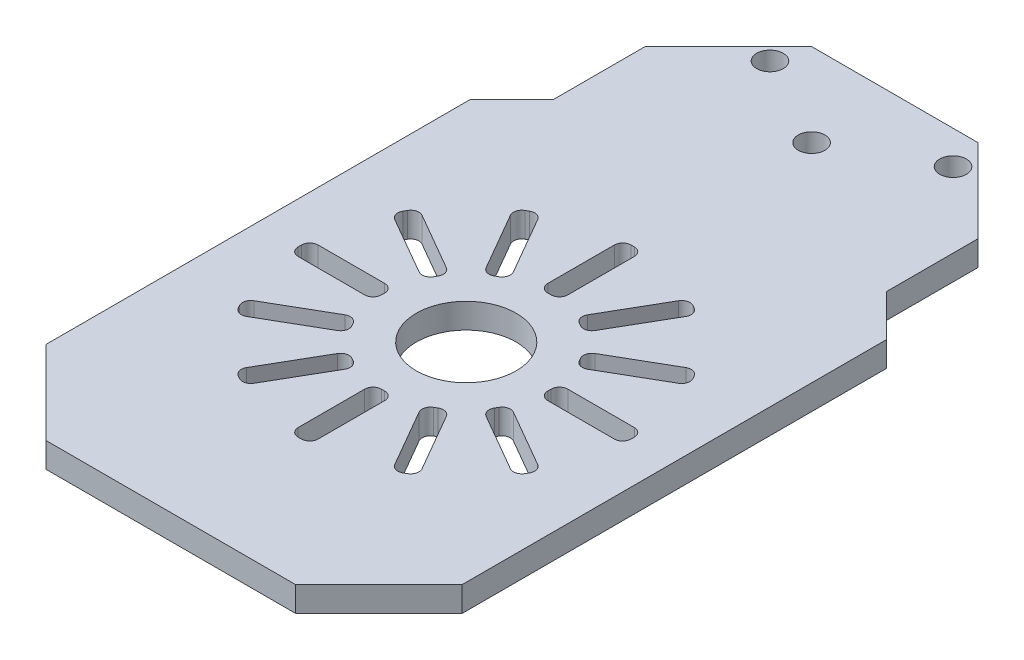
SolidWorks part; units mm, degrees
material "Thornel Mat VMA"
ref_plane "前视基准面" through (0, 0, 0) normal (0, 0, 1) x (1, 0, 0)
ref_plane "上视基准面" through (0, 0, 0) normal (0, 1, 0) x (1, 0, 0)
ref_plane "右视基准面" through (0, 0, 0) normal (1, 0, 0) x (0, 0, -1)
sketch "草图1" plane through (0, 0, 0) normal (0, 1, 0) x (1, 0, 0)
  line L0 (0, -1000) -> (0, 49000) construction
  line L1 (-20, 8) -> (20, 8)
  line L2 (-20, 8) -> (-20, -8)
  line L3 (-20, -8) -> (20, -8)
  line L4 (20, 8) -> (20, -8)
  line L5 (-20, 8) -> (20, -8) construction
  line L6 (-20, -8) -> (20, 8) construction
  line L7 (-25, -79) -> (25, -79)
  line L8 (-25, -79) -> (-25, -8)
  line L9 (-25, -8) -> (25, -8)
  line L10 (25, -79) -> (25, -8)
  line L11 (-25, -79) -> (25, -8) construction
  line L12 (-25, -8) -> (25, -79) construction
  circle A0 centre (-11, 4) radius 1.6
  circle A1 centre (0, -2) radius 1.6
  circle A2 centre (11, 4) radius 1.6
  point P0 (0, 0)
  point P6 (0, -43.5)
  dimension "D3" = 3.2
  dimension "D4" = 3.2
  dimension "D1" = 16
  dimension "D2" = 40
  dimension "D5" = 6
  dimension "D6" = 4
  dimension "D7" = 11
  dimension "D8" = 71
  dimension "D9" = 50
extrude "凸台-拉伸1" add sketch "草图1" along normal blind 3 contours L7 L10 L9 L3 L8 | L4 L1 L2 L3 A0 A1 A2 region at (0, 0, 0.0784) region at (0, 0, 43.5)
chamfer "倒角1" distance 10 angle 45 6 edges at (-25, 1.5, 8) (25, 1.5, 8) (-20, 1.5, -8) (20, 1.5, -8) (25, 1.5, 79) (-25, 1.5, 79)
sketch "草图2" [suppressed] plane through (0, 3, 0) normal (0, 1, 0) x (1, 0, 0)
  line L0 (0, -1000) -> (0, 49000) construction
  line L1 (18, -71.4131) -> (12, -26.4131) construction
  line L2 (-7.5, -15.8094) -> (7.5, -15.8094)
  line L3 (-7.5, -15.8094) -> (-7.5, -25.8094)
  line L4 (-7.5, -25.8094) -> (7.5, -25.8094)
  line L5 (7.5, -15.8094) -> (7.5, -25.8094)
  line L6 (-7.5, -15.8094) -> (7.5, -25.8094) construction
  line L7 (-7.5, -25.8094) -> (7.5, -15.8094) construction
  line L8 (-18, -26.4131) -> (-12, -26.4131)
  line L9 (-18, -26.4131) -> (-18, -71.4131)
  line L10 (-18, -71.4131) -> (-12, -71.4131)
  line L11 (-12, -26.4131) -> (-12, -71.4131)
  line L12 (-18, -26.4131) -> (-12, -71.4131) construction
  line L13 (-18, -71.4131) -> (-12, -26.4131) construction
  line L14 (18, -26.4131) -> (12, -71.4131) construction
  line L15 (12, -26.4131) -> (12, -71.4131)
  line L16 (18, -71.4131) -> (12, -71.4131)
  line L17 (18, -26.4131) -> (18, -71.4131)
  line L18 (18, -26.4131) -> (12, -26.4131)
  point P1 (0, -20.8094)
  point P8 (-15, -48.9131)
  point P17 (15, -48.9131)
  dimension "D1" = 15
  dimension "D2" = 10
  dimension "D3" = 15
  dimension "D4" = 6
  dimension "D5" = 45
sketch "草图3" plane through (0, 3, 0) normal (0, 1, 0) x (1, 0, 0)
  line L0 (-25, -18) -> (25, -69) construction
  line L1 (0, -43.5) -> (0, -58.5) construction
  line L2 (-6.5392, -52.4263) -> (-10.5392, -59.3545)
  line L3 (-0.2, -53.5) -> (0.2, -53.5)
  line L4 (-1.2, -54.5) -> (-1.2, -62.5)
  line L5 (-0.2, -63.5) -> (0.2, -63.5)
  line L6 (1.2, -54.5) -> (1.2, -62.5)
  line L7 (-1.2, -53.5) -> (1.2, -63.5) construction
  line L8 (-1.2, -63.5) -> (1.2, -53.5) construction
  line L9 (-4.4608, -53.6263) -> (-8.4608, -60.5545)
  line L10 (-5.1732, -52.0603) -> (-4.8268, -52.2603)
  line L11 (-10.1732, -60.7205) -> (-9.8268, -60.9205)
  line L12 (-10.1263, -47.9608) -> (-17.0545, -51.9608)
  line L13 (-8.9263, -50.0392) -> (-15.8545, -54.0392)
  line L14 (-8.7603, -48.3268) -> (-8.5603, -48.6732)
  line L15 (-17.4205, -53.3268) -> (-17.2205, -53.6732)
  line L16 (-11, -42.3) -> (-19, -42.3)
  line L17 (-11, -44.7) -> (-19, -44.7)
  line L18 (-10, -43.3) -> (-10, -43.7)
  line L19 (-20, -43.3) -> (-20, -43.7)
  line L20 (-8.9263, -36.9608) -> (-15.8545, -32.9608)
  line L21 (-10.1263, -39.0392) -> (-17.0545, -35.0392)
  line L22 (-8.5603, -38.3268) -> (-8.7603, -38.6732)
  line L23 (-17.2205, -33.3268) -> (-17.4205, -33.6732)
  line L24 (-4.4608, -33.3737) -> (-8.4608, -26.4455)
  line L25 (-6.5392, -34.5737) -> (-10.5392, -27.6455)
  line L26 (-4.8268, -34.7397) -> (-5.1732, -34.9397)
  line L27 (-9.8268, -26.0795) -> (-10.1732, -26.2795)
  line L28 (1.2, -32.5) -> (1.2, -24.5)
  line L29 (-1.2, -32.5) -> (-1.2, -24.5)
  line L30 (0.2, -33.5) -> (-0.2, -33.5)
  line L31 (0.2, -23.5) -> (-0.2, -23.5)
  line L32 (6.5392, -34.5737) -> (10.5392, -27.6455)
  line L33 (4.4608, -33.3737) -> (8.4608, -26.4455)
  line L34 (5.1732, -34.9397) -> (4.8268, -34.7397)
  line L35 (10.1732, -26.2795) -> (9.8268, -26.0795)
  line L36 (10.1263, -39.0392) -> (17.0545, -35.0392)
  line L37 (8.9263, -36.9608) -> (15.8545, -32.9608)
  line L38 (8.7603, -38.6732) -> (8.5603, -38.3268)
  line L39 (17.4205, -33.6732) -> (17.2205, -33.3268)
  line L40 (11, -44.7) -> (19, -44.7)
  line L41 (11, -42.3) -> (19, -42.3)
  line L42 (10, -43.7) -> (10, -43.3)
  line L43 (20, -43.7) -> (20, -43.3)
  line L44 (8.9263, -50.0392) -> (15.8545, -54.0392)
  line L45 (10.1263, -47.9608) -> (17.0545, -51.9608)
  line L46 (8.5603, -48.6732) -> (8.7603, -48.3268)
  line L47 (17.2205, -53.6732) -> (17.4205, -53.3268)
  line L48 (4.4608, -53.6263) -> (8.4608, -60.5545)
  line L49 (6.5392, -52.4263) -> (10.5392, -59.3545)
  line L50 (4.8268, -52.2603) -> (5.1732, -52.0603)
  line L51 (9.8268, -60.9205) -> (10.1732, -60.7205)
  line L52 (0, -43.5) -> (-0.2, -53.5) construction
  circle A0 centre (0, -43.5) radius 6
  arc A1 (0.2, -63.5) -> (1.2, -62.5) centre (0.2, -62.5) ccw
  arc A2 (-1.2, -62.5) -> (-0.2, -63.5) centre (-0.2, -62.5) ccw
  arc A3 (0.2, -53.5) -> (1.2, -54.5) centre (0.2, -54.5) cw
  arc A4 (-0.2, -53.5) -> (-1.2, -54.5) centre (-0.2, -54.5) ccw
  arc A5 (-5.1732, -52.0603) -> (-6.5392, -52.4263) centre (-5.6732, -52.9263) ccw
  arc A6 (-4.8268, -52.2603) -> (-4.4608, -53.6263) centre (-5.3268, -53.1263) cw
  arc A7 (-9.8268, -60.9205) -> (-8.4608, -60.5545) centre (-9.3268, -60.0545) ccw
  arc A8 (-10.5392, -59.3545) -> (-10.1732, -60.7205) centre (-9.6732, -59.8545) ccw
  arc A9 (-8.7603, -48.3268) -> (-10.1263, -47.9608) centre (-9.6263, -48.8268) ccw
  arc A10 (-8.5603, -48.6732) -> (-8.9263, -50.0392) centre (-9.4263, -49.1732) cw
  arc A11 (-17.2205, -53.6732) -> (-15.8545, -54.0392) centre (-16.3545, -53.1732) ccw
  arc A12 (-17.0545, -51.9608) -> (-17.4205, -53.3268) centre (-16.5545, -52.8268) ccw
  arc A13 (-10, -43.3) -> (-11, -42.3) centre (-11, -43.3) ccw
  arc A14 (-10, -43.7) -> (-11, -44.7) centre (-11, -43.7) cw
  arc A15 (-20, -43.7) -> (-19, -44.7) centre (-19, -43.7) ccw
  arc A16 (-19, -42.3) -> (-20, -43.3) centre (-19, -43.3) ccw
  arc A17 (-8.5603, -38.3268) -> (-8.9263, -36.9608) centre (-9.4263, -37.8268) ccw
  arc A18 (-8.7603, -38.6732) -> (-10.1263, -39.0392) centre (-9.6263, -38.1732) cw
  arc A19 (-17.4205, -33.6732) -> (-17.0545, -35.0392) centre (-16.5545, -34.1732) ccw
  arc A20 (-15.8545, -32.9608) -> (-17.2205, -33.3268) centre (-16.3545, -33.8268) ccw
  arc A21 (-4.8268, -34.7397) -> (-4.4608, -33.3737) centre (-5.3268, -33.8737) ccw
  arc A22 (-5.1732, -34.9397) -> (-6.5392, -34.5737) centre (-5.6732, -34.0737) cw
  arc A23 (-10.1732, -26.2795) -> (-10.5392, -27.6455) centre (-9.6732, -27.1455) ccw
  arc A24 (-8.4608, -26.4455) -> (-9.8268, -26.0795) centre (-9.3268, -26.9455) ccw
  arc A25 (0.2, -33.5) -> (1.2, -32.5) centre (0.2, -32.5) ccw
  arc A26 (-0.2, -33.5) -> (-1.2, -32.5) centre (-0.2, -32.5) cw
  arc A27 (-0.2, -23.5) -> (-1.2, -24.5) centre (-0.2, -24.5) ccw
  arc A28 (1.2, -24.5) -> (0.2, -23.5) centre (0.2, -24.5) ccw
  arc A29 (5.1732, -34.9397) -> (6.5392, -34.5737) centre (5.6732, -34.0737) ccw
  arc A30 (4.8268, -34.7397) -> (4.4608, -33.3737) centre (5.3268, -33.8737) cw
  arc A31 (9.8268, -26.0795) -> (8.4608, -26.4455) centre (9.3268, -26.9455) ccw
  arc A32 (10.5392, -27.6455) -> (10.1732, -26.2795) centre (9.6732, -27.1455) ccw
  arc A33 (8.7603, -38.6732) -> (10.1263, -39.0392) centre (9.6263, -38.1732) ccw
  arc A34 (8.5603, -38.3268) -> (8.9263, -36.9608) centre (9.4263, -37.8268) cw
  arc A35 (17.2205, -33.3268) -> (15.8545, -32.9608) centre (16.3545, -33.8268) ccw
  arc A36 (17.0545, -35.0392) -> (17.4205, -33.6732) centre (16.5545, -34.1732) ccw
  arc A37 (10, -43.7) -> (11, -44.7) centre (11, -43.7) ccw
  arc A38 (10, -43.3) -> (11, -42.3) centre (11, -43.3) cw
  arc A39 (20, -43.3) -> (19, -42.3) centre (19, -43.3) ccw
  arc A40 (19, -44.7) -> (20, -43.7) centre (19, -43.7) ccw
  arc A41 (8.5603, -48.6732) -> (8.9263, -50.0392) centre (9.4263, -49.1732) ccw
  arc A42 (8.7603, -48.3268) -> (10.1263, -47.9608) centre (9.6263, -48.8268) cw
  arc A43 (17.4205, -53.3268) -> (17.0545, -51.9608) centre (16.5545, -52.8268) ccw
  arc A44 (15.8545, -54.0392) -> (17.2205, -53.6732) centre (16.3545, -53.1732) ccw
  arc A45 (4.8268, -52.2603) -> (4.4608, -53.6263) centre (5.3268, -53.1263) ccw
  arc A46 (5.1732, -52.0603) -> (6.5392, -52.4263) centre (5.6732, -52.9263) cw
  arc A47 (10.1732, -60.7205) -> (10.5392, -59.3545) centre (9.6732, -59.8545) ccw
  arc A48 (8.4608, -60.5545) -> (9.8268, -60.9205) centre (9.3268, -60.0545) ccw
  point P13 (0, -43.5)
  dimension "D1" = 12
  dimension "D5" = 1
  dimension "D2" = 15
  dimension "D3" = 2.4
  dimension "D4" = 10
  dimension "D7" = 10.002
  dimension "D6" = 12
extrude "切除-拉伸1" cut sketch "草图3" against normal blind 10
